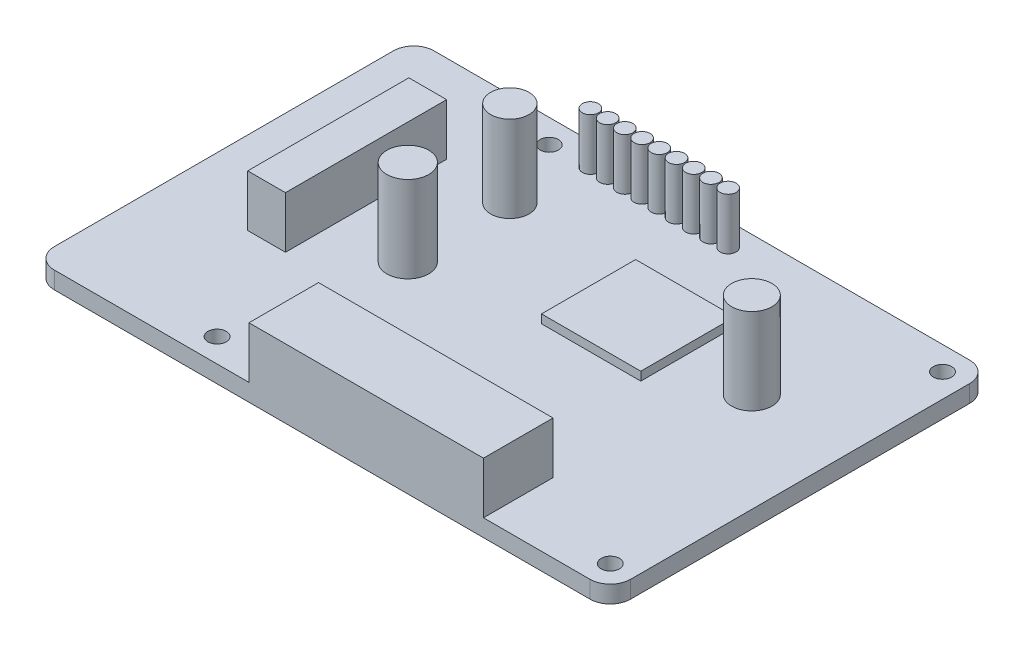
SolidWorks part; units mm, degrees
material "Silicon Dioxide"
ref_plane "Front" through (0, 0, 0) normal (0, 0, 1) x (1, 0, 0)
ref_plane "Top" through (0, 0, 0) normal (0, 1, 0) x (1, 0, 0)
ref_plane "Right" through (0, 0, 0) normal (1, 0, 0) x (0, 0, -1)
ref_axis "Axis1" through (0, 0, 55) along (0, 0, -1)
sketch "Sketch1" plane through (0, 0, 0) normal (0, 1, 0) x (1, 0, 0)
  line L0 (39.5, 28) -> (-39.5, 28)
  line L1 (-42.5, 25) -> (-42.5, -25)
  line L2 (-39.5, -28) -> (39.5, -28)
  line L3 (42.5, -25) -> (42.5, 25)
  circle A0 centre (39, -24.5) radius 3
  arc A1 (42.5, 25) -> (39.5, 28) centre (39.5, 25) ccw
  arc A2 (-39.5, 28) -> (-42.5, 25) centre (-39.5, 25) ccw
  arc A3 (-42.5, -25) -> (-39.5, -28) centre (-39.5, -25) ccw
  arc A4 (39.5, -28) -> (42.5, -25) centre (39.5, -25) ccw
  circle A5 centre (-19, 24.5) radius 3
  circle A6 centre (-19, 24.5) radius 1.35
  circle A7 centre (-19, -24.5) radius 1.35
  circle A8 centre (-19, -24.5) radius 3
  circle A9 centre (39, 24.5) radius 3
  circle A10 centre (39, 24.5) radius 1.35
  circle A11 centre (39, -24.5) radius 1.35
  dimension "D1" = 2.7
  dimension "D2" = 6
  dimension "D3" = 39
  dimension "D4" = 42.5
  dimension "D5" = 19
  dimension "D6" = 42.5
  dimension "D7" = 24.5
  dimension "D8" = 28
  dimension "D9" = 24.5
  dimension "D10" = 28
extrude "Boss-Extrude1" add sketch "Sketch1" along normal blind 2.54 contours A8 A7 | A5 A6 | L2 A4 L3 A1 L0 A2 L1 A3 A9 A8 A5 A0 | A9 A10 | A0 A11 region at (-0.2438, 0, 0) region at (36.0849, 0, 24.5) region at (-21.9151, 0, -24.5) region at (-21.9151, 0, 24.5) region at (36.0849, 0, -24.5)
sketch "Sketch2" plane through (0, 2.54, 0) normal (0, 1, 0) x (1, 0, 0)
  line L0 (-39.5, -28) -> (39.5, -28) construction
  line L1 (-10.7963, -17.7403) -> (23.7946, -17.7403)
  line L2 (-10.7963, -17.7403) -> (-10.7963, -28)
  line L3 (-10.7963, -28) -> (23.7946, -28)
  line L4 (23.7946, -17.7403) -> (23.7946, -28)
  line L5 (-10.7963, -17.7403) -> (23.7946, -28) construction
  line L6 (-10.7963, -28) -> (23.7946, -17.7403) construction
  line L7 (42.5, -25) -> (42.5, 25) construction
  point P4 (6.4992, -22.8702)
  dimension "D1" = 18.7054
  dimension "D2" = 36.0008
  dimension "D3" = 5.1298
extrude "Boss-Extrude2" add sketch "Sketch2" along normal blind 7.62
sketch "Sketch3" plane through (0, 2.54, 0) normal (0, 1, 0) x (1, 0, 0)
  line L0 (42.5, -25) -> (42.5, 25) construction
  line L1 (-24.721, 15.078) -> (-30.2919, 15.078)
  line L2 (-24.721, 15.078) -> (-24.721, -8.6912)
  line L3 (-24.721, -8.6912) -> (-30.2919, -8.6912)
  line L4 (-30.2919, 15.078) -> (-30.2919, -8.6912)
  line L5 (-24.721, 15.078) -> (-30.2919, -8.6912) construction
  line L6 (-24.721, -8.6912) -> (-30.2919, 15.078) construction
  line L7 (39.5, 28) -> (-39.5, 28) construction
  point P4 (-27.5064, 3.1934)
  dimension "D1" = 67.221
  dimension "D2" = 70.0064
  dimension "D3" = 12.922
  dimension "D4" = 24.8066
extrude "Boss-Extrude3" add sketch "Sketch3" along normal blind 7.62
sketch "Sketch4" plane through (0, 2.54, 0) normal (0, 1, 0) x (1, 0, 0)
  line L1 (3.2966, 14.9369) -> (17.9361, 14.9369)
  line L2 (3.2966, 14.9369) -> (3.2966, 1.0575)
  line L3 (3.2966, 1.0575) -> (17.9361, 1.0575)
  line L4 (17.9361, 14.9369) -> (17.9361, 1.0575)
  line L5 (3.2966, 14.9369) -> (17.9361, 1.0575) construction
  line L6 (3.2966, 1.0575) -> (17.9361, 14.9369) construction
  point P4 (10.6164, 7.9972)
extrude "Boss-Extrude4" add sketch "Sketch4" along normal blind 1.27
sketch "Sketch5" plane through (0, 2.54, 0) normal (0, 1, 0) x (1, 0, 0)
  line L0 (42.5, -25) -> (42.5, 25) construction
  line L1 (39.5, 28) -> (-39.5, 28) construction
  circle A0 centre (-13.0195, 24.5866) radius 1.1809
  circle A1 centre (-10.4795, 24.5866) radius 1.1809
  circle A2 centre (-7.9395, 24.5866) radius 1.1809
  circle A3 centre (-5.3995, 24.5866) radius 1.1809
  circle A4 centre (-2.8595, 24.5866) radius 1.1809
  circle A5 centre (-0.3195, 24.5866) radius 1.1809
  circle A6 centre (2.2205, 24.5866) radius 1.1809
  circle A7 centre (4.7605, 24.5866) radius 1.1809
  circle A8 centre (7.3005, 24.5866) radius 1.1809
  dimension "D2" = 2.3618
  dimension "D3" = 35.1995
  dimension "D4" = 37.7395
  dimension "D5" = 3.4134
  dimension "D1" = 9
extrude "Boss-Extrude5" add sketch "Sketch5" along normal blind 7.62
sketch "Sketch6" plane through (0, 2.54, 0) normal (0, 1, 0) x (1, 0, 0)
  line L0 (42.5, -25) -> (42.5, 25) construction
  line L1 (39.5, 28) -> (-39.5, 28) construction
  circle A0 centre (-14.4893, 14.1724) radius 2.8377
  circle A1 centre (-14.4893, -0.8787) radius 3.0935
  circle A2 centre (27.8334, 7.5375) radius 2.9746
  dimension "D1" = 6.187
  dimension "D2" = 5.6755
  dimension "D3" = 5.9492
  dimension "D4" = 14.6666
  dimension "D5" = 56.9893
  dimension "D6" = 13.8276
  dimension "D7" = 20.4625
  dimension "D8" = 28.8787
extrude "Boss-Extrude6" add sketch "Sketch6" along normal blind 12.7
